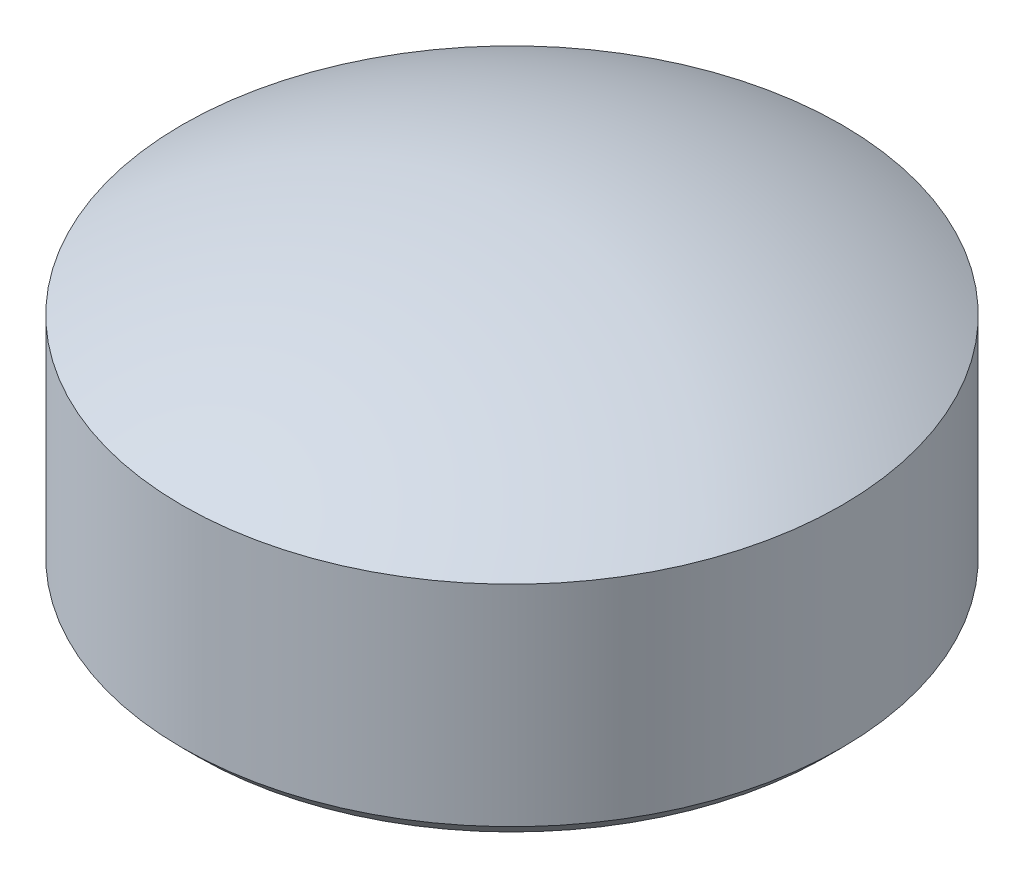
SolidWorks part; units mm, degrees
material "1.0301 (C10)"
ref_plane "Front Plane" through (0, 0, 0) normal (0, 0, 1) x (1, 0, 0)
ref_plane "Top Plane" through (0, 0, 0) normal (0, 1, 0) x (1, 0, 0)
ref_plane "Right Plane" through (0, 0, 0) normal (1, 0, 0) x (0, 0, -1)
sketch "Sketch1" plane through (0, 0, 0) normal (0, 0, 1) x (1, 0, 0)
  line L0 (0, 10) -> (0, -11)
  line L1 (0, -11) -> (-21, -11)
  arc A0 (0, 10) -> (-21, -11) centre (0, -11) ccw
  dimension "D1" = 21
  dimension "D2" = 10
revolve "Revolve1" add sketch "Sketch1" angle 360 about L0
sketch "Sketch2" plane through (0, 0, 0) normal (0, 1, 0) x (1, 0, 0)
  circle A0 centre (0, 0) radius 21
  circle A1 centre (0, 0) radius 21 construction
  circle A2 centre (0, 0) radius 10.5
  dimension "D1" = 21
extrude "Cut-Extrude1" cut sketch "Sketch2" along normal through all both and the other way through all
extrude "Cut-Extrude2" cut sketch "Sketch2<5>" against normal through all contours A2
sketch "Sketch2<5>" plane through (0, 0, 0) normal (0, 1, 0) x (1, 0, 0) same geometry as "Sketch2"
chamfer "Chamfer1" distance 0.5 angle 45 1 edges at (0, 0, 10.5)
